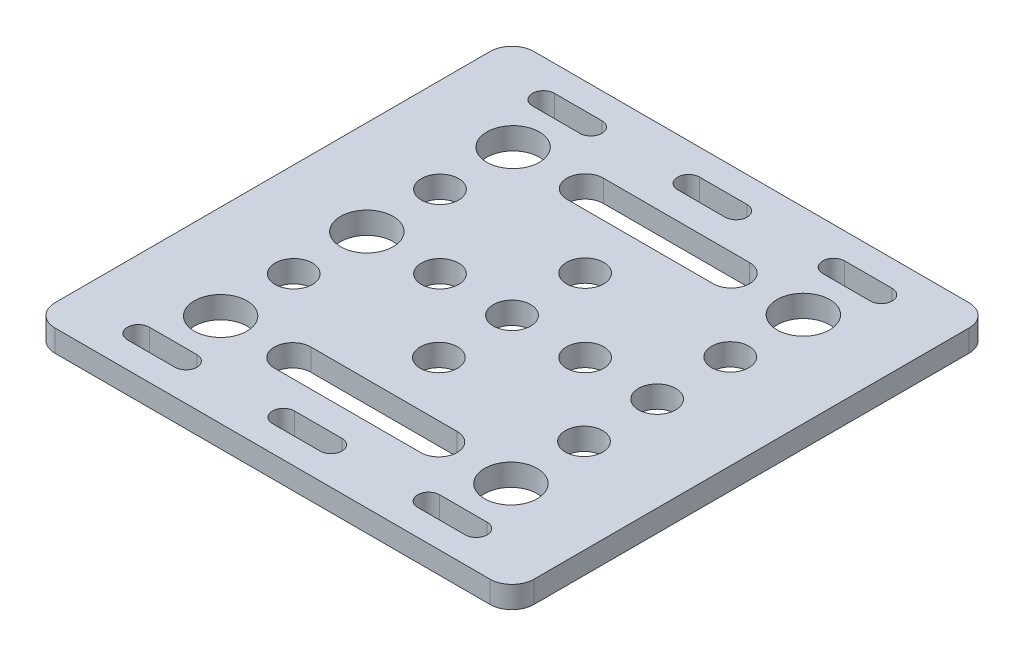
SolidWorks part; units mm, degrees
ref_plane "Płaszczyzna przednia" through (0, 0, 0) normal (0, 0, 1) x (1, 0, 0)
ref_plane "Płaszczyzna górna" through (0, 0, 0) normal (0, 1, 0) x (1, 0, 0)
ref_plane "Płaszczyzna prawa" through (0, 0, 0) normal (1, 0, 0) x (0, 0, -1)
sketch "Szkic1" plane through (0, 0, 0) normal (0, 1, 0) x (1, 0, 0)
  line L0 (9.35, 60.45) -> (15.85, 60.45) construction
  line L1 (3, 0) -> (62.5, 0)
  line L2 (0, 3) -> (0, 62.5)
  line L3 (3, 65.5) -> (62.5, 65.5)
  line L4 (65.5, 3) -> (65.5, 62.5)
  line L5 (9.35, 61.95) -> (15.85, 61.95)
  line L6 (9.35, 58.95) -> (15.85, 58.95)
  line L7 (29.2, 58.95) -> (35.7, 58.95)
  line L8 (29.2, 61.95) -> (35.7, 61.95)
  line L9 (29.2, 60.45) -> (35.7, 60.45) construction
  line L10 (49.05, 58.95) -> (55.55, 58.95)
  line L11 (49.05, 61.95) -> (55.55, 61.95)
  line L12 (49.05, 60.45) -> (55.55, 60.45) construction
  line L13 (29.2, 3.55) -> (35.7, 3.55)
  line L14 (29.2, 6.55) -> (35.7, 6.55)
  line L15 (29.2, 5.05) -> (35.7, 5.05) construction
  line L16 (49.05, 3.55) -> (55.55, 3.55)
  line L17 (49.05, 6.55) -> (55.55, 6.55)
  line L18 (49.05, 5.05) -> (55.55, 5.05) construction
  line L19 (9.35, 3.55) -> (15.85, 3.55)
  line L20 (9.35, 6.55) -> (15.85, 6.55)
  line L21 (9.35, 5.05) -> (15.85, 5.05) construction
  line L22 (22.75, 12.75) -> (42.75, 12.75) construction
  line L23 (22.75, 15.25) -> (42.75, 15.25)
  line L24 (22.75, 10.25) -> (42.75, 10.25)
  line L25 (22.75, 50.25) -> (42.75, 50.25)
  line L26 (22.75, 55.25) -> (42.75, 55.25)
  line L27 (22.75, 52.75) -> (42.75, 52.75) construction
  arc A0 (9.35, 61.95) -> (9.35, 58.95) centre (9.35, 60.45) ccw
  arc A1 (15.85, 58.95) -> (15.85, 61.95) centre (15.85, 60.45) ccw
  arc A2 (29.2, 61.95) -> (29.2, 58.95) centre (29.2, 60.45) ccw
  arc A3 (35.7, 58.95) -> (35.7, 61.95) centre (35.7, 60.45) ccw
  arc A4 (49.05, 61.95) -> (49.05, 58.95) centre (49.05, 60.45) ccw
  arc A5 (55.55, 58.95) -> (55.55, 61.95) centre (55.55, 60.45) ccw
  arc A6 (29.2, 6.55) -> (29.2, 3.55) centre (29.2, 5.05) ccw
  arc A7 (35.7, 3.55) -> (35.7, 6.55) centre (35.7, 5.05) ccw
  arc A8 (49.05, 6.55) -> (49.05, 3.55) centre (49.05, 5.05) ccw
  arc A9 (55.55, 3.55) -> (55.55, 6.55) centre (55.55, 5.05) ccw
  arc A10 (9.35, 6.55) -> (9.35, 3.55) centre (9.35, 5.05) ccw
  arc A11 (15.85, 3.55) -> (15.85, 6.55) centre (15.85, 5.05) ccw
  circle A16 centre (12.9, 32.75) radius 3.6
  circle A19 centre (12.9, 42.75) radius 2.55
  circle A20 centre (32.75, 42.75) radius 2.55
  circle A21 centre (52.6, 42.75) radius 2.55
  circle A22 centre (32.75, 32.75) radius 2.55
  circle A23 centre (52.6, 32.75) radius 2.55
  circle A24 centre (32.75, 22.75) radius 2.55
  circle A25 centre (52.6, 22.75) radius 2.55
  circle A27 centre (12.9, 22.75) radius 2.55
  circle A28 centre (12.9, 32.75) radius 2.55 [skipped]
  circle A29 centre (42.75, 32.75) radius 2.55
  circle A30 centre (42.75, 32.75) radius 2.55
  circle A31 centre (22.9, 32.75) radius 2.55
  arc A32 (0, 62.5) -> (3, 65.5) centre (3, 62.5) cw
  arc A33 (62.5, 65.5) -> (65.5, 62.5) centre (62.5, 62.5) cw
  arc A34 (62.5, 0) -> (65.5, 3) centre (62.5, 3) ccw
  arc A35 (3, 0) -> (0, 3) centre (3, 3) cw
  arc A36 (22.75, 15.25) -> (22.75, 10.25) centre (22.75, 12.75) ccw
  arc A37 (42.75, 10.25) -> (42.75, 15.25) centre (42.75, 12.75) ccw
  arc A38 (22.75, 55.25) -> (22.75, 50.25) centre (22.75, 52.75) ccw
  arc A39 (42.75, 50.25) -> (42.75, 55.25) centre (42.75, 52.75) ccw
  point P7 (12.6, 60.45)
  point P17 (32.45, 60.45)
  point P24 (52.3, 60.45)
  point P31 (32.45, 5.05)
  point P38 (52.3, 5.05)
  point P45 (12.6, 5.05)
  point P87 (65.5, 65.5)
  point P90 (65.5, 0)
  point P93 (0, 0)
  point P96 (32.75, 12.75)
  point P101 (0, 0)
  point P104 (32.75, 52.75)
  dimension "D14" = 5.1
  dimension "D15" = 12.9
  dimension "D16" = 22.75
  dimension "D21" = 3
  dimension "D1" = 65.5
  dimension "D2" = 65.5
  dimension "D3" = 9.35
  dimension "D4" = 6.5
  dimension "D5" = 5.05
  dimension "D6" = 3
  dimension "D22" = 5
  dimension "D23" = 32.75
  dimension "D24" = 20
  dimension "D25" = 52.75
  dimension "D7" = 3
  dimension "D8" = 2
  dimension "D17" = 3
  dimension "D18" = 3
  dimension "D19" = 2
  dimension "D20" = 2
  dimension "D26" = 2
extrude "Dodanie-wyciągnięcie1" add sketch "Szkic1" along normal blind 3 contours A35 L1 A34 L4 A33 L3 A32 L2 A39 L25 A38 L26 A37 L24 A36 L23 A31 A29 A27 A25 A24 A23 A22 A21 A20 A19 A16 A11 L19 region at (1.5337, 0, -1.5337)
hole_wizard "Otwory ustalające Ø10.0mm1" positions "Szkic2" profile "Szkic3" hole size "Ø10.0" standard "Ansi Metric"
sketch "Szkic2" plane through (0, 3, 0) normal (0, 1, 0) x (1, 0, 0)
  point P0 (12.9, 12.75)
  point P3 (12.9, 52.75)
  point P6 (52.6, 12.75)
  point P9 (52.6, 52.75)
sketch "Szkic3" plane through (12.9, 3, -12.75) normal (1, 0, 0) x (0, 0, 1)
  line L0 (0, 0) -> (0, 13.6631)
  line L1 (0, 13.6631) -> (3.6, 11.5)
  line L2 (3.6, 11.5) -> (3.6, 0)
  line L5 (3.6, 0) -> (0, 0)
  line L10 (0, 13.6631) -> (-3.6, 11.5) construction
  line L11 (0, -6.35) -> (0, 107.95) construction
  dimension "Œrednica otworu" = 7.2
  dimension "G³êbokoœæ otworu" = 11.5
  dimension "K¹t wiert³a" = 118
